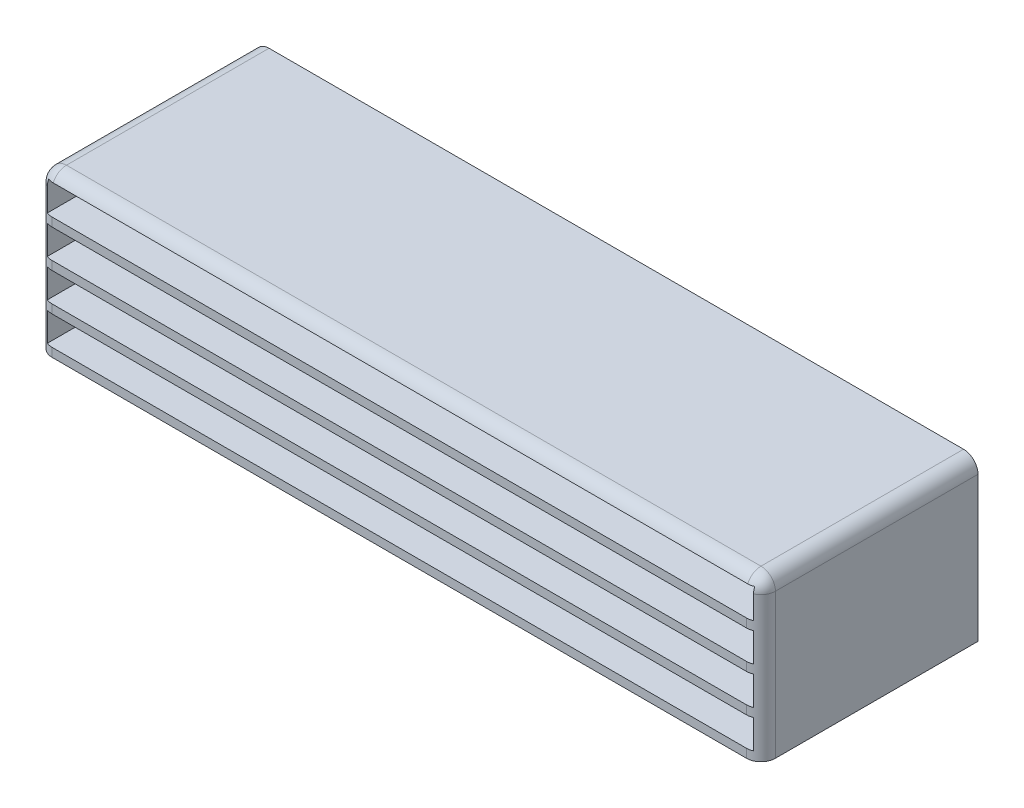
SolidWorks part; units mm, degrees
ref_plane "Front Plane" through (0, 0, 0) normal (0, 0, 1) x (1, 0, 0)
ref_plane "Top Plane" through (0, 0, 0) normal (0, 1, 0) x (1, 0, 0)
ref_plane "Right Plane" through (0, 0, 0) normal (1, 0, 0) x (0, 0, -1)
sketch "Sketch1" plane through (0, 0, 0) normal (0, 0, 1) x (1, 0, 0)
  line L0 (-81.8543, 78.9541) -> (-81.8543, 75.9541)
  line L3 (-81.8543, 23.9541) -> (168.1457, 23.9541)
  line L4 (168.1457, 78.9541) -> (168.1457, 23.9541)
  line L5 (-81.8543, 75.9541) -> (-81.8543, 65.9541)
  line L6 (-81.8543, 65.9541) -> (-81.8543, 62.9541)
  line L7 (-81.8543, 62.9541) -> (-81.8543, 52.9541)
  line L8 (-81.8543, 52.9541) -> (-81.8543, 49.9541)
  line L9 (-81.8543, 49.9541) -> (-81.8543, 39.9541)
  line L10 (-81.8543, 39.9541) -> (-81.8543, 36.9541)
  line L11 (-81.8543, 36.9541) -> (-81.8543, 26.9541)
  line L12 (-81.8543, 26.9541) -> (-81.8543, 23.9541)
  line L13 (-81.8543, 75.9541) -> (168.1457, 75.9541)
  line L14 (-81.8543, 65.9541) -> (168.1457, 65.9541)
  line L15 (-81.8543, 62.9541) -> (168.1457, 62.9541)
  line L16 (-81.8543, 52.9541) -> (168.1457, 52.9541)
  line L17 (-81.8543, 49.9541) -> (168.1457, 49.9541)
  line L18 (-81.8543, 39.9541) -> (168.1457, 39.9541)
  line L19 (-81.8543, 36.9541) -> (168.1457, 36.9541)
  line L20 (-81.8543, 26.9541) -> (168.1457, 26.9541)
  line L21 (-81.8543, 78.9541) -> (-78.8543, 78.9541)
  line L22 (-78.8543, 78.9541) -> (165.1457, 78.9541)
  line L23 (165.1457, 78.9541) -> (168.1457, 78.9541)
  line L24 (-78.8543, 78.9541) -> (-78.8543, 23.9541)
  line L25 (165.1457, 78.9541) -> (165.1457, 23.9541)
  dimension "D1" = 250
  dimension "D2" = 3
  dimension "D3" = 10
  dimension "D4" = 3
  dimension "D5" = 3
extrude "Boss-Extrude1" add sketch "Sketch1" along normal blind 3 contours L24 L21 L0 L13 | L24 L13 L5 L14 | L24 L14 L6 L15 | L24 L15 L7 L16 | L24 L16 L8 L17 | L24 L17 L9 L18 | L24 L18 L10 L19 | L24 L19 L11 L20 | L24 L20 L12 L3 | L25 L20 L24 L3 | L25 L19 L24 L20 | L25 L18 L24 L19 | L25 L17 L24 L18 | L25 L16 L24 L17 | L25 L15 L24 L16 | L25 L14 L24 L15 | L25 L13 L24 L14 | L25 L22 L24 L13 | L23 L25 L13 L4 | L13 L25 L14 L4 | L14 L25 L15 L4 | L15 L25 L16 L4 | L16 L25 L17 L4 | L17 L25 L18 L4 | L18 L25 L19 L4 | L19 L25 L20 L4 | L20 L25 L3 L4 region at (-80.3543, 77.4541, 0) region at (-80.3543, 70.9541, 0) region at (43.1457, 77.4541, 0) region at (-80.3543, 64.4541, 0) region at (43.1457, 70.9541, 0) region at (166.6457, 77.4541, 0) region at (-80.3543, 57.9541, 0) region at (43.1457, 64.4541, 0) region at (166.6457, 70.9541, 0) region at (-80.3543, 51.4541, 0) region at (43.1457, 57.9541, 0) region at (166.6457, 64.4541, 0) region at (-80.3543, 44.9541, 0) region at (43.1457, 51.4541, 0) region at (166.6457, 57.9541, 0) region at (-80.3543, 38.4541, 0) region at (43.1457, 44.9541, 0) region at (166.6457, 51.4541, 0) region at (-80.3543, 31.9541, 0) region at (43.1457, 38.4541, 0) region at (166.6457, 44.9541, 0) region at (-80.3543, 25.4541, 0) region at (43.1457, 31.9541, 0) region at (166.6457, 38.4541, 0) region at (43.1457, 25.4541, 0) region at (166.6457, 31.9541, 0) region at (166.6457, 25.4541, 0)
extrude "Boss-Extrude2" add sketch "Sketch1<4>" along normal blind 75 contours L24 L21 L0 L13 | L24 L13 L5 L14 | L24 L14 L6 L15 | L24 L15 L7 L16 | L24 L16 L8 L17 | L24 L17 L9 L18 | L25 L16 L24 L17 | L25 L14 L24 L15 | L25 L22 L24 L13 | L24 L18 L10 L19 | L24 L19 L11 L20 | L24 L20 L12 L3 | L25 L20 L24 L3 | L25 L18 L24 L19 | L23 L25 L13 L4 | L13 L25 L14 L4 | L14 L25 L15 L4 | L15 L25 L16 L4 | L16 L25 L17 L4 | L17 L25 L18 L4 | L18 L25 L19 L4 | L19 L25 L20 L4 | L20 L25 L3 L4 region at (-80.3543, 77.4541, 0) region at (-80.3543, 70.9541, 0) region at (43.1457, 77.4541, 0) region at (-80.3543, 64.4541, 0) region at (166.6457, 77.4541, 0) region at (-80.3543, 57.9541, 0) region at (43.1457, 64.4541, 0) region at (166.6457, 70.9541, 0) region at (-80.3543, 51.4541, 0) region at (166.6457, 64.4541, 0) region at (-80.3543, 44.9541, 0) region at (43.1457, 51.4541, 0) region at (166.6457, 57.9541, 0) region at (-80.3543, 38.4541, 0) region at (166.6457, 51.4541, 0) region at (-80.3543, 31.9541, 0) region at (43.1457, 38.4541, 0) region at (166.6457, 44.9541, 0) region at (-80.3543, 25.4541, 0) region at (166.6457, 38.4541, 0) region at (43.1457, 25.4541, 0) region at (166.6457, 31.9541, 0) region at (166.6457, 25.4541, 0)
sketch "Sketch1<4>" plane through (0, 0, 0) normal (0, 0, 1) x (1, 0, 0) same geometry as "Sketch1"
fillet "Fillet1" radius 5 2 edges at (168.1457, 78.9541, 37.5) (-81.8543, 78.9541, 37.5)
fillet "Fillet2" radius 5 2 edges at (168.1457, 48.9541, 75) (-81.8543, 48.9541, 75)
